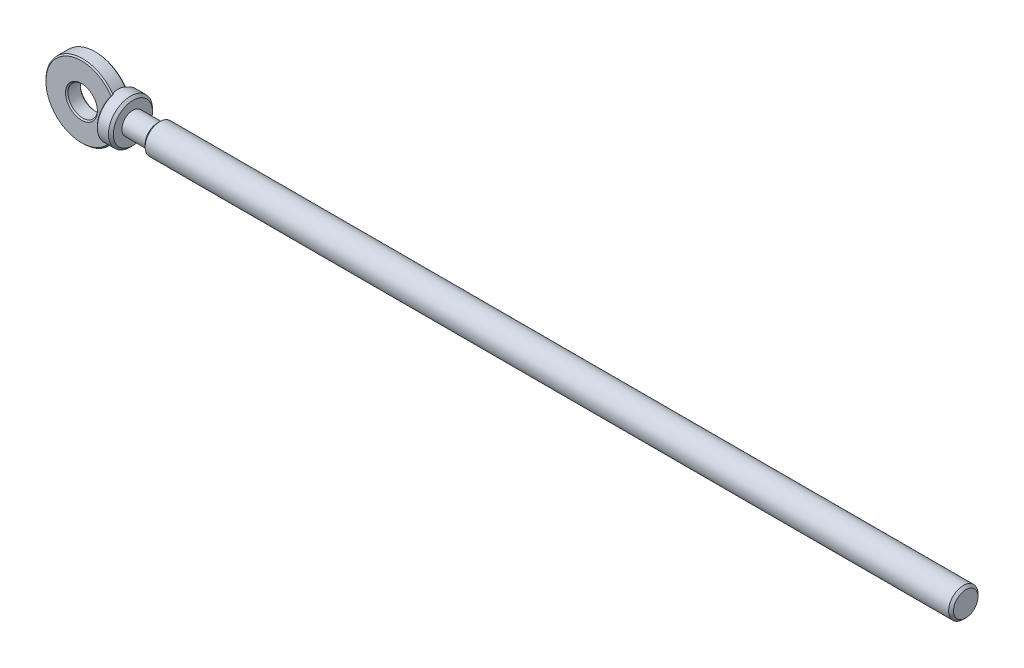
SolidWorks part; units mm, degrees
ref_plane "正面" through (0, 0, 0) normal (0, 0, 1) x (1, 0, 0)
ref_plane "平面" through (0, 0, 0) normal (0, 1, 0) x (1, 0, 0)
ref_plane "右側面" through (0, 0, 0) normal (1, 0, 0) x (0, 0, -1)
sketch "ｽｹｯﾁ1" plane through (0, 0, 0) normal (0, 0, 1) x (1, 0, 0)
  circle A0 centre (0, 0) radius 15
  circle A1 centre (0, 0) radius 6
  dimension "D1" = 30
  dimension "D2" = 12
extrude "ﾎﾞｽ - 押し出し1" add sketch "ｽｹｯﾁ1" along normal mid plane 6
sketch "ｽｹｯﾁ2" plane through (0, 0, 0) normal (0, 0, 1) x (1, 0, 0)
  line L0 (-15, 0) -> (12, 0) construction
  line L2 (12, 0) -> (18, 0)
  line L3 (12, 0) -> (12, 9)
  line L4 (12, 9) -> (18, 9)
  line L5 (18, 0) -> (18, 9)
  circle A0 centre (0, 0) radius 15 construction
  dimension "D1" = 6
  dimension "D2" = 9
  dimension "D3" = 12
revolve "回転1" add sketch "ｽｹｯﾁ2" angle 360 about L0
sketch "ｽｹｯﾁ3" plane through (18, 0, 0) normal (1, 0, 0) x (0, 0, -1)
  circle A0 centre (0, 0) radius 4.5
  dimension "D1" = 9
extrude "ﾎﾞｽ - 押し出し2" add sketch "ｽｹｯﾁ3" along normal blind 10
sketch "ｽｹｯﾁ4" plane through (28, 0, 0) normal (1, 0, 0) x (0, 0, -1)
  circle A0 centre (0, 0) radius 6
  dimension "D1" = 12
extrude "ﾎﾞｽ - 押し出し3" add sketch "ｽｹｯﾁ4" along normal blind 330
chamfer "面取り1" distance 1 angle 45 3 edges at (18, 0, 9) (28, 0, -6) (358, 0, -6)
chamfer "面取り2" distance 0.5 angle 45 4 edges at (-15, 0, 3) (-15, 0, -3) (6, 0, 3) (6, 0, -3)
chamfer "面取り3" distance 0.5 angle 45 2 edges at (12, 0, 9) (12, 0, -9)
